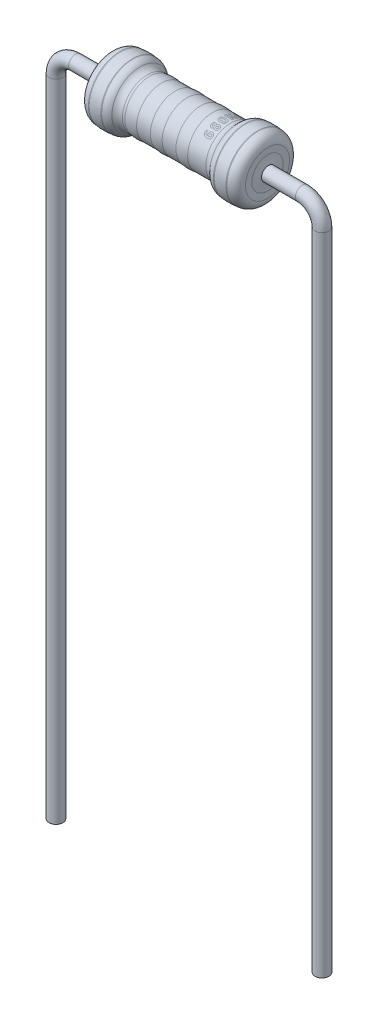
SolidWorks part; units mm, degrees
material "Plain Carbon Steel"
ref_plane "Front Plane" through (0, 0, 0) normal (0, 0, 1) x (1, 0, 0)
ref_plane "Top Plane" through (0, 0, 0) normal (0, 1, 0) x (1, 0, 0)
ref_plane "Right Plane" through (0, 0, 0) normal (1, 0, 0) x (0, 0, -1)
sketch "Sketch1" plane through (0, 0, 0) normal (0, 0, 1) x (1, 0, 0)
  line L0 (-4.33, 0) -> (4.33, 0)
  line L1 (-5.08, -0.75) -> (-5.08, -25.4)
  line L2 (5.08, -0.75) -> (5.08, -25.4)
  line L3 (-5.08, -25.4) -> (5.08, -25.4) construction
  line L4 (0, 0) -> (0, -25.4) construction
  arc A0 (-4.33, 0) -> (-5.08, -0.75) centre (-4.33, -0.75) ccw
  arc A1 (4.33, 0) -> (5.08, -0.75) centre (4.33, -0.75) cw
  dimension "D2" = 0.75
  dimension "D1" = 10.16
  dimension "D3" = 25.4
ref_plane "Plane1" through (-5.08, -25.4, 0) normal (0, -1, 0) x (-1, 0, 0)
sketch "Sketch2" plane through (-5.08, -25.4, 0) normal (0, -1, 0) x (-1, 0, 0)
  circle A0 centre (0, 0) radius 0.265
  dimension "D1" = 0.53
sweep "Sweep1" add profiles "Sketch2" path "Sketch1"
sketch "Sketch3" plane through (0, 0, 0) normal (0, 0, 1) x (1, 0, 0)
  line L0 (-3, 0) -> (3, 0)
  line L5 (-3, 0) -> (-3, 1.2)
  line L6 (3, 0) -> (3, 1.2)
  line L7 (-3, 1.2) -> (-1.8, 1.2)
  line L8 (3, 1.2) -> (1.8, 1.2)
  line L9 (-1.8, 1.2) -> (-1.8, 0.95)
  line L10 (-1.8, 0.95) -> (1.8, 0.95)
  line L11 (1.8, 0.95) -> (1.8, 1.2)
  line L12 (0, 0) -> (0, 0.95) construction
  dimension "D1" = 6
  dimension "D2" = 1.2
  dimension "D3" = 3.6
  dimension "D4" = 0.95
  dimension "D5" = 0.25
revolve "Revolve1" add sketch "Sketch3" angle 360 about L0
fillet "Fillet-1" radius 0.35 2 edges at (1.8, 0, 1.2) (-1.8, 0, 1.2)
fillet "Fillet-2" radius 0.36 4 edges at (3, 0, 1.2) (-3, 0, 1.2) (1.8, 0, 0.95) (-1.8, 0, 0.95)
sketch "Sketch5" plane through (0, 0, 0) normal (0, 0, 1) x (1, 0, 0)
  line L0 (-2.64, -1.2) -> (-2.1354, -1.2) construction
  line L5 (-2.3877, -1.2) -> (-2.3877, 0) construction
  line L10 (-3, 1.2) -> (-1.8, 1.2) construction
  line L15 (-1.05, 0.95) -> (-0.525, 0.95) construction
  line L16 (-3, 0) -> (3, 0) construction
  line L17 (-2.6127, 1.2) -> (-2.1627, 1.2) construction
  line L18 (-2.6127, 1.2) -> (-2.6127, 0) construction
  line L19 (-2.6127, 0) -> (-2.1627, 0) construction
  line L20 (-2.1627, 1.2) -> (-2.1627, 0) construction
  line L21 (-1.8, 0.95) -> (1.8, 0.95) construction
  line L22 (2.6127, 1.2) -> (2.1627, 1.2) construction
  line L23 (2.6127, 1.2) -> (2.6127, 0) construction
  line L24 (2.6127, 0) -> (2.1627, 0) construction
  line L25 (2.1627, 1.2) -> (2.1627, 0) construction
  line L26 (-1.05, 0.95) -> (-1.5, 0.95) construction
  line L27 (-1.05, 0.95) -> (-1.05, 0) construction
  line L28 (-1.05, 0) -> (-1.5, 0) construction
  line L29 (-1.5, 0.95) -> (-1.5, 0) construction
  line L30 (-2.3877, 1.2) -> (-2.3877, 1.22) construction
  line L31 (-0.075, 0.95) -> (-0.525, 0.95) construction
  line L32 (-0.075, 0.95) -> (-0.075, 0) construction
  line L33 (-0.075, 0) -> (-0.525, 0) construction
  line L34 (-0.525, 0.95) -> (-0.525, 0) construction
  line L35 (-1.275, 0.95) -> (-1.275, 0.97) construction
  line L36 (-0.3, 0.95) -> (-0.3, 0.97) construction
  line L37 (2.3877, 1.2) -> (2.3877, 1.22) construction
  line L39 (2.1354, -1.2) -> (2.64, -1.2) construction
  line L41 (2.3877, -1.2) -> (2.3877, 0) construction
  line L44 (3, 1.2) -> (1.8, 1.2) construction
  line L46 (-0.075, 0.95) -> (0.45, 0.95) construction
  line L48 (-3, 0) -> (-3, 0.6)
  line L49 (-3, 0) -> (-3, 1.2) construction
  line L50 (-3, 0) -> (-3.05, 0)
  line L51 (-3.05, 0) -> (-3.05, 0.2)
  line L52 (3, 0) -> (3.05, 0)
  line L53 (3.05, 0) -> (3.05, 0.2)
  line L54 (3, 0) -> (3, 0.6)
  line L55 (3, 0) -> (3, 1.2) construction
  line L56 (-1.05, 0) -> (-0.525, 0) construction
  line L58 (-0.075, 0) -> (0.45, 0) construction
  line L59 (0.45, 0) -> (0.45, 0.95) construction
  line L60 (0.45, 0) -> (0.9, 0) construction
  line L61 (0.9, 0) -> (0.9, 0.95) construction
  line L62 (1.5946, 0.95) -> (-1.5946, 0.95) construction
  line L63 (0.9, 0.95) -> (0.45, 0.95) construction
  line L64 (0.675, 0.95) -> (0.675, 0.97) construction
  arc A0 (-2.6127, 1.2) -> (-2.1627, 1.2) centre (-2.3877, -0.0556) cw construction
  arc A1 (-1.5, 0.95) -> (-1.05, 0.95) centre (-1.275, -0.3056) cw construction
  arc A2 (-0.525, 0.95) -> (-0.075, 0.95) centre (-0.3, -0.3056) cw construction
  arc A3 (2.1627, 1.2) -> (2.6127, 1.2) centre (2.3877, -0.0556) cw construction
  arc A6 (-3, 0.6) -> (-3.05, 0.2) centre (-4.625, 0.6) cw
  arc A7 (3.05, 0.2) -> (3, 0.6) centre (4.625, 0.6) cw
  arc A8 (0.45, 0.95) -> (0.9, 0.95) centre (0.675, -0.3056) cw construction
  dimension "D4" = 0.02
  dimension "D5" = 0.05
  dimension "D7" = 0.6
  dimension "D2" = 1.5
  dimension "D3" = 2.4
  dimension "D1" = 0.45
  dimension "D6" = 0.2
revolve "Revolve Ends" add sketch "Sketch5" angle 360 about L19
sketch "Sketch12" plane through (0, 0, 0) normal (0, 0, 1) x (1, 0, 0)
  line L0 (-2.6127, 0) -> (-2.1627, 0) construction
  line L1 (-2.6127, 0) -> (-2.1627, 0)
  line L2 (-2.6127, 1.2) -> (-2.6127, 0) construction
  line L3 (-2.6127, 1.2) -> (-2.6127, 0)
  line L4 (-2.1627, 1.2) -> (-2.1627, 0) construction
  line L5 (-2.1627, 1.2) -> (-2.1627, 0)
  arc A0 (-2.1627, 1.2) -> (-2.6127, 1.2) centre (-2.3877, -0.0556) ccw construction
  arc A1 (-2.1627, 1.2) -> (-2.6127, 1.2) centre (-2.3877, -0.0556) ccw
revolve "Revolve BAND 1" add sketch "Sketch12" angle 360 about L19
sketch "Sketch7" plane through (0, 0, 0) normal (0, 0, 1) x (1, 0, 0)
  line L0 (-1.05, 0) -> (-1.5, 0) construction
  line L1 (-1.05, 0.95) -> (-1.05, 0) construction
  line L2 (-1.5, 0.95) -> (-1.5, 0) construction
  line L3 (-1.05, 0.95) -> (-1.05, 0)
  line L4 (-1.5, 0.95) -> (-1.5, 0)
  line L5 (-1.05, 0) -> (-1.5, 0)
  arc A0 (-1.05, 0.95) -> (-1.5, 0.95) centre (-1.275, -0.3056) ccw construction
  arc A1 (-1.05, 0.95) -> (-1.5, 0.95) centre (-1.275, -0.3056) ccw
revolve "Revolve BAND 2" add sketch "Sketch7" angle 360 about L28
sketch "Sketch8" plane through (0, 0, 0) normal (0, 0, 1) x (1, 0, 0)
  line L0 (-0.075, 0.95) -> (-0.075, 0) construction
  line L1 (-0.075, 0) -> (-0.525, 0) construction
  line L2 (-0.525, 0.95) -> (-0.525, 0) construction
  line L3 (-0.075, 0.95) -> (-0.075, 0)
  line L4 (-0.075, 0) -> (-0.525, 0)
  line L5 (-0.525, 0.95) -> (-0.525, 0)
  arc A0 (-0.075, 0.95) -> (-0.525, 0.95) centre (-0.3, -0.3056) ccw construction
  arc A1 (-0.075, 0.95) -> (-0.525, 0.95) centre (-0.3, -0.3056) ccw
revolve "Revolve BAND 3" add sketch "Sketch8" angle 360 about L33
sketch "Sketch9" plane through (0, 0, 0) normal (0, 0, 1) x (1, 0, 0)
  line L0 (0.9, 0) -> (0.9, 0.95) construction
  line L1 (0.45, 0) -> (0.45, 0.95) construction
  line L2 (0.45, 0) -> (0.9, 0) construction
  line L3 (0.9, 0) -> (0.9, 0.95)
  line L4 (0.45, 0) -> (0.45, 0.95)
  line L5 (0.45, 0) -> (0.9, 0)
  arc A0 (0.9, 0.95) -> (0.45, 0.95) centre (0.675, -0.3056) ccw construction
  arc A1 (0.9, 0.95) -> (0.45, 0.95) centre (0.675, -0.3056) ccw
revolve "Revolve BAND 4" add sketch "Sketch9" angle 360 about L60
sketch "Sketch11" plane through (0, 0, 0) normal (0, 0, 1) x (1, 0, 0)
  line L0 (2.6127, 1.2) -> (2.6127, 0) construction
  line L1 (2.1627, 1.2) -> (2.1627, 0) construction
  line L2 (2.6127, 0) -> (2.1627, 0) construction
  line L3 (2.6127, 1.2) -> (2.6127, 0)
  line L4 (2.1627, 1.2) -> (2.1627, 0)
  line L5 (2.6127, 0) -> (2.1627, 0)
  arc A0 (2.6127, 1.2) -> (2.1627, 1.2) centre (2.3877, -0.0556) ccw construction
  arc A1 (2.6127, 1.2) -> (2.1627, 1.2) centre (2.3877, -0.0556) ccw
revolve "Revolve5" add sketch "Sketch11" angle 360 about L24
ref_plane "Plane2" through (0, 2, 0) normal (0, 1, 0) x (1, 0, 0)
sketch "Sketch6" plane through (0, 2, 0) normal (0, 1, 0) x (1, 0, 0)
  line L0 (0, 0) -> (1.5, 0) construction
  line L1 (1.5, 1) -> (1.5, -1) construction
  text T0 "680KΩ" font "Calibri" height 0.3
  dimension "D1" = 1.5
  dimension "D2" = 2
wrap "Wrap1" sketch "Sketch6" wrap type scribe source sketch "Sketch6" face at (1.5946, 0, 0.95)
